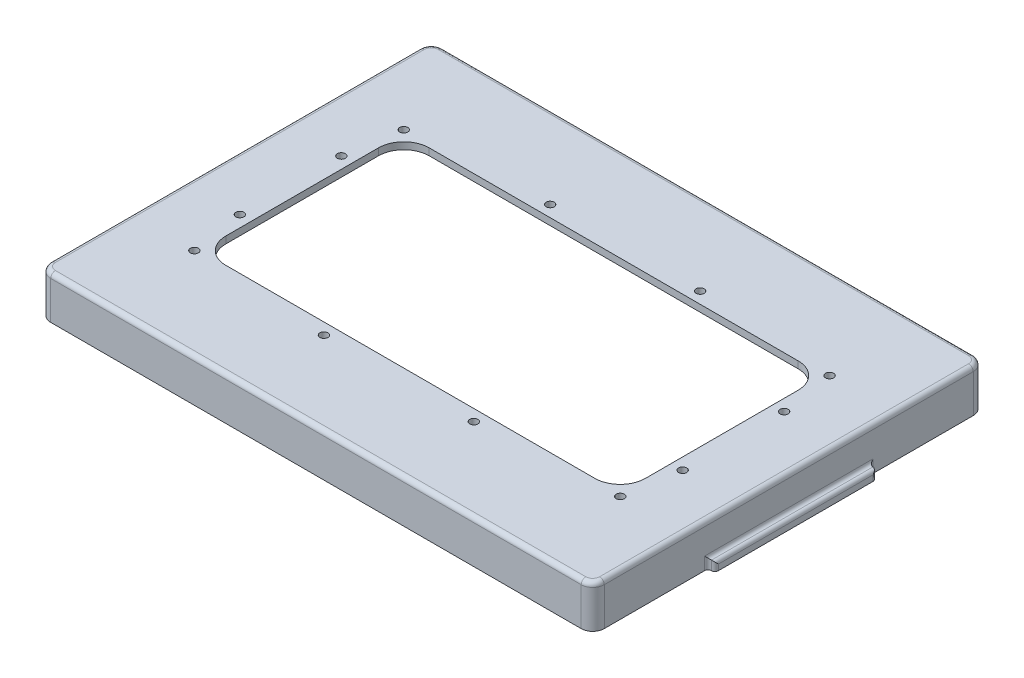
SolidWorks part; units mm, degrees
ref_plane "前视基准面" through (0, 0, 0) normal (0, 0, 1) x (1, 0, 0)
ref_plane "上视基准面" through (0, 0, 0) normal (0, 1, 0) x (1, 0, 0)
ref_plane "右视基准面" through (0, 0, 0) normal (1, 0, 0) x (0, 0, -1)
other "Configuration Table"
sketch "草图1" plane through (0, 0, 0) normal (0, 1, 0) x (1, 0, 0)
  line L1 (-115, 85) -> (115, 85)
  line L2 (-120, 80) -> (-120, -80)
  line L3 (-115, -85) -> (115, -85)
  line L4 (120, 80) -> (120, -80)
  line L5 (-120, 85) -> (120, -85) construction
  line L6 (-120, -85) -> (120, 85) construction
  line L7 (-112.5, 82.5) -> (112.5, 82.5)
  line L8 (-117.5, 77.5) -> (-117.5, -77.5)
  line L9 (-112.5, -82.5) -> (112.5, -82.5)
  line L10 (117.5, 77.5) -> (117.5, -77.5)
  line L11 (-117.5, 82.5) -> (117.5, -82.5) construction
  line L12 (-117.5, -82.5) -> (117.5, 82.5) construction
  arc A0 (112.5, 82.5) -> (117.5, 77.5) centre (112.5, 77.5) cw
  arc A1 (115, 85) -> (120, 80) centre (115, 80) cw
  arc A2 (115, -85) -> (120, -80) centre (115, -80) ccw
  arc A3 (112.5, -82.5) -> (117.5, -77.5) centre (112.5, -77.5) ccw
  arc A4 (-120, -80) -> (-115, -85) centre (-115, -80) ccw
  arc A5 (-117.5, -77.5) -> (-112.5, -82.5) centre (-112.5, -77.5) ccw
  arc A6 (-112.5, 82.5) -> (-117.5, 77.5) centre (-112.5, 77.5) ccw
  arc A7 (-115, 85) -> (-120, 80) centre (-115, 80) ccw
  point P0 (0, 0)
  point P6 (0, 0)
  dimension "D5" = 5
  dimension "D1" = 170
  dimension "D2" = 240
  dimension "D3" = 2.5
  dimension "D4" = 2.5
extrude "凸台-拉伸1" add sketch "草图1" along normal blind 15.5
sketch "草图3" plane through (0, 15.5, 0) normal (0, 1, 0) x (1, 0, 0)
  line L0 (-120, 80) -> (-120, -80) construction
  line L1 (-115, -85) -> (115, -85) construction
  line L2 (120, -80) -> (120, 80) construction
  line L3 (115, 85) -> (-115, 85) construction
  line L4 (-120, 80) -> (-120, -80)
  line L5 (-115, -85) -> (115, -85)
  line L6 (120, -80) -> (120, 80)
  line L7 (115, 85) -> (-115, 85)
  arc A0 (-120, -80) -> (-115, -85) centre (-115, -80) ccw construction
  arc A1 (115, -85) -> (120, -80) centre (115, -80) ccw construction
  arc A2 (120, 80) -> (115, 85) centre (115, 80) ccw construction
  arc A3 (-115, 85) -> (-120, 80) centre (-115, 80) ccw construction
  arc A4 (-120, -80) -> (-115, -85) centre (-115, -80) ccw
  arc A5 (115, -85) -> (120, -80) centre (115, -80) ccw
  arc A6 (120, 80) -> (115, 85) centre (115, 80) ccw
  arc A7 (-115, 85) -> (-120, 80) centre (-115, 80) ccw
extrude "凸台-拉伸2" add sketch "草图3" along normal blind 3
fillet "圆角2" radius 2 16 edges at (-116.0355, 15.5, -81.0355) (0, 15.5, -82.5) (116.0355, 15.5, -81.0355) (117.5, 15.5, 0) (116.0355, 15.5, 81.0355) (0, 15.5, 82.5) (-116.0355, 15.5, 81.0355) (-117.5, 15.5, 0) (-118.5355, 18.5, -83.5355) (0, 18.5, -85) (118.5355, 18.5, -83.5355) (120, 18.5, 0) (118.5355, 18.5, 83.5355) (0, 18.5, 85) (-118.5355, 18.5, 83.5355) (-120, 18.5, 0)
sketch "草图4" plane through (0, 0, 0) normal (0, -1, 0) x (1, 0, 0)
  line L0 (132.0996, 0) -> (-141.453, 0) construction
  line L1 (0, 91.6674) -> (0, -90.9145) construction
  line L2 (-120, -80) -> (-120, 80) construction
  line L3 (-120, 35) -> (-123, 35)
  line L4 (-120, 35) -> (-120, -35)
  line L5 (-120, -35) -> (-123, -35)
  line L6 (-123, 35) -> (-123, -35)
  line L7 (120, 80) -> (120, -80) construction
  line L8 (120, 35) -> (123, 35)
  line L9 (120, 35) -> (120, -35)
  line L10 (120, -35) -> (123, -35)
  line L11 (123, 35) -> (123, -35)
  dimension "D1" = 3
  dimension "D2" = 70
extrude "凸台-拉伸3" add sketch "草图4" against normal blind 4
fillet "圆角3" radius 1.5 12 edges at (120, 4, 0) (-120, 4, 0) (-123, 4, 0) (123, 4, 0) (120, 2, -35) (123, 2, -35) (123, 2, 35) (120, 2, 35) (-120, 2, -35) (-123, 2, -35) (-123, 2, 35) (-120, 2, 35)
sketch "草图9" plane through (0, 18.5, -20.5) normal (0, -1, 0) x (1, 0, 0)
  line L0 (-59.0069, 20.5) -> (47.6905, 20.5) construction
  line L1 (0, 44.1827) -> (0, -8.8935) construction
  circle A0 centre (-32.5, 69.55) radius 1.75
  circle A1 centre (-95.9968, 42.5) radius 1.75
  circle A2 centre (-32.5, -28.55) radius 1.75
  circle A3 centre (-95.9968, -1.5) radius 1.75
  circle A4 centre (32.5, -28.55) radius 1.75
  circle A5 centre (95.9968, -1.5) radius 1.75
  circle A6 centre (32.5, 69.55) radius 1.75
  circle A7 centre (95.9968, 42.5) radius 1.75
  point P2 (0, -8.8935)
  point P20 (0, 44.1827)
  dimension "D1" = 3.5
  dimension "D2" = 22
  dimension "D3" = 65
  dimension "D4" = 98.1
  dimension "D5" = 191.9936
sketch "草图10" plane through (0, 18.5, -20.5) normal (0, -1, 0) x (1, 0, 0)
  line L0 (0, 108.5164) -> (0, -67.8757) construction
  line L1 (-38.7093, 20.5) -> (34.3983, 20.5) construction
  circle A0 centre (-92.3252, 65.8784) radius 1.75
  circle A1 centre (92.3252, 65.8784) radius 1.75
  circle A2 centre (92.3252, -24.8784) radius 1.75
  circle A3 centre (-92.3252, -24.8784) radius 1.75
  dimension "D1" = 3.5
  dimension "D2" = 90.7569
  dimension "D3" = 184.6504
sketch "草图5" plane through (0, 18.5, 0) normal (0, 1, 0) x (1, 0, 0)
  line L1 (-89.5, -54.55) -> (89.5, -54.55)
  line L2 (-101.5, -42.55) -> (-101.5, 42.55)
  line L3 (-89.5, 54.55) -> (89.5, 54.55)
  line L4 (101.5, -42.55) -> (101.5, 42.55)
  line L5 (-101.5, -54.55) -> (101.5, 54.55) construction
  line L6 (-101.5, 54.55) -> (101.5, -54.55) construction
  line L7 (80, -44.1) -> (-80, -44.1)
  line L8 (91, -33.1) -> (91, 33.1)
  line L9 (80, 44.1) -> (-80, 44.1)
  line L10 (-91, -33.1) -> (-91, 33.1)
  line L11 (91, -44.1) -> (-91, 44.1) construction
  line L12 (91, 44.1) -> (-91, -44.1) construction
  arc A0 (89.5, 54.55) -> (101.5, 42.55) centre (89.5, 42.55) cw
  arc A1 (89.5, -54.55) -> (101.5, -42.55) centre (89.5, -42.55) ccw
  arc A2 (-89.5, -54.55) -> (-101.5, -42.55) centre (-89.5, -42.55) cw
  arc A3 (-101.5, 42.55) -> (-89.5, 54.55) centre (-89.5, 42.55) cw
  arc A4 (91, 33.1) -> (80, 44.1) centre (80, 33.1) ccw
  arc A5 (80, -44.1) -> (91, -33.1) centre (80, -33.1) ccw
  arc A6 (-80, -44.1) -> (-91, -33.1) centre (-80, -33.1) cw
  arc A7 (-80, 44.1) -> (-91, 33.1) centre (-80, 33.1) ccw
  point P0 (0, 0)
  point P6 (0, 0)
  dimension "D5" = 12
  dimension "D6" = 11
  dimension "D1" = 203
  dimension "D2" = 109.1
  dimension "D3" = 88.2
  dimension "D4" = 182
extrude "切除-拉伸3" cut sketch "草图5" against normal through all contours L9 A7 L10 A6 L7 A5 L8 A4 region at (0, 18.5, 0)
extrude "切除-拉伸4" cut sketch "草图10" along normal through all
extrude "切除-拉伸5" cut sketch "草图9" along direction (0, 1, 0) on the side of the normal through all
